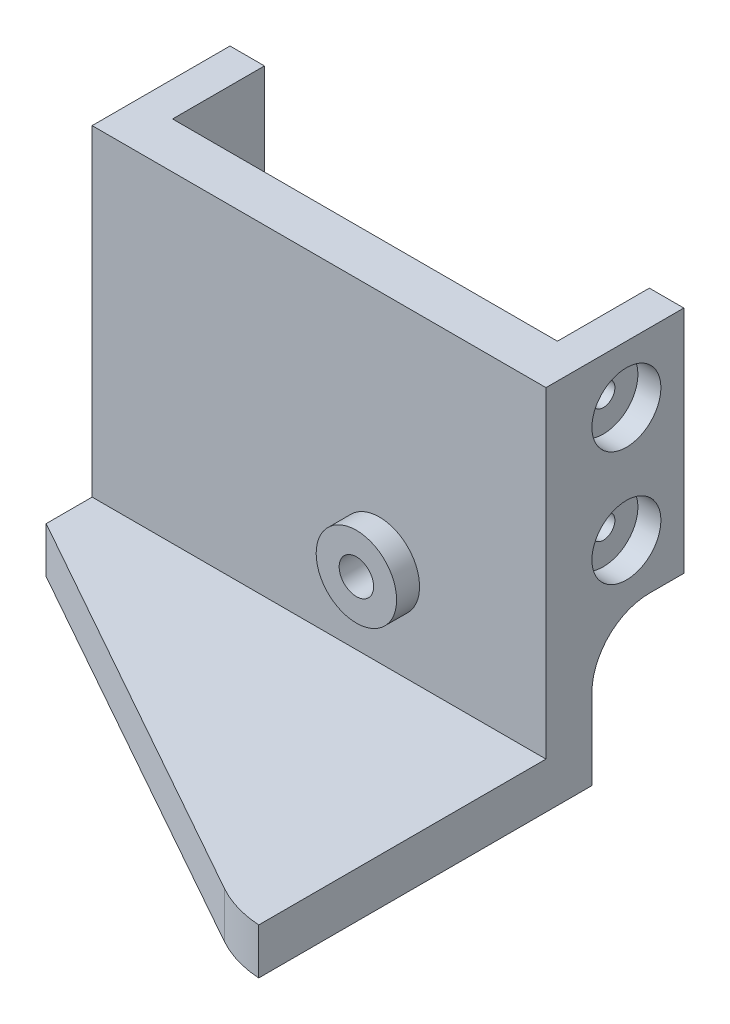
SolidWorks part; units mm, degrees
ref_plane "Front Plane" through (0, 0, 0) normal (0, 0, 1) x (1, 0, 0)
ref_plane "Top Plane" through (0, 0, 0) normal (0, 1, 0) x (1, 0, 0)
ref_plane "Right Plane" through (0, 0, 0) normal (1, 0, 0) x (0, 0, -1)
sketch "Sketch1" plane through (0, 0, 0) normal (0, 1, 0) x (1, 0, 0)
  line L1 (0, 0) -> (37.5, 0)
  line L2 (0, 0) -> (0, 12)
  line L3 (0, 12) -> (37.5, 12)
  line L4 (37.5, 0) -> (37.5, 12)
  line L5 (3, 12) -> (36.5, 12)
  line L6 (3, 12) -> (3, 4)
  line L7 (3, 4) -> (36.5, 4)
  line L8 (36.5, 12) -> (36.5, 4)
  dimension "D1" = 12
  dimension "D2" = 37.5
  dimension "D3" = 33.5
  dimension "D4" = 3
  dimension "D5" = 3
  dimension "10" = 8
extrude "Boss-Extrude1" add sketch "Sketch1" along normal blind 20 contours L3 L8 L7 L6 L2 L1 L4 region at (17.2775, 0, -3.0549)
sketch "Sketch2" plane through (0, 0, 0) normal (0, -1, 0) x (1, 0, 0)
  line L0 (37.5, 0) -> (37.5, -12) construction
  line L1 (0, 0) -> (37.5, 0)
  line L2 (0, 0) -> (0, -4)
  line L3 (0, -4) -> (37.5, -4)
  line L4 (37.5, 0) -> (37.5, -4)
extrude "Boss-Extrude2" add sketch "Sketch2" along normal blind 12
fillet "Fillet1" radius 5 2 edges at (1.5, 0, -4) (37, 0, -4)
sketch "Sketch3" plane through (0, 0, 0) normal (0, 0, 1) x (1, 0, 0)
  line L0 (37.5, 20) -> (37.5, -12) construction
  line L1 (0, -12) -> (37.5, -12)
  line L2 (0, -12) -> (0, -8)
  line L3 (0, -8) -> (37.5, -8)
  line L4 (37.5, -12) -> (37.5, -8)
  dimension "D1" = 4
extrude "Boss-Extrude3" add sketch "Sketch3" along normal blind 25 contours L3 L4 L1 L2
sketch "Sketch4" plane through (0, 0, 0) normal (0, 0, 1) x (1, 0, 0)
  line L0 (0, -8) -> (37.5, -8) construction
  line L1 (0, 20) -> (0, -8) construction
  circle A0 centre (25, -0.5) radius 1.5
  circle A1 centre (25, -0.5) radius 3.5
  dimension "D1" = 3
  dimension "D2" = 7.5
  dimension "D4" = 25
  dimension "D3" = 2
extrude "Boss-Extrude4" add sketch "Sketch4" along normal blind 2
sketch "Sketch5" plane through (0, 0, 2) normal (0, 0, 1) x (1, 0, 0)
  circle A0 centre (25, -0.5) radius 1.5 construction
  circle A1 centre (25, -0.5) radius 1.5
extrude "Cut-Extrude1" cut sketch "Sketch5" against normal through all contours A1
sketch "Sketch6" plane through (0, -8, 0) normal (0, 1, 0) x (1, 0, 0)
  line L0 (37.5, -25) -> (0, -4)
  line L3 (0, -25) -> (0, 0) construction
  line L4 (0, -4) -> (0, -25)
  line L5 (0, -25) -> (37.5, -25)
  dimension "D1" = 4
extrude "Cut-Extrude2" cut sketch "Sketch6" against normal blind 10
sketch "Sketch8" plane through (37.5, 0, 0) normal (1, 0, 0) x (0, 0, -1)
  circle A0 centre (7, 15) radius 1
  circle A1 centre (7, 5) radius 1
  dimension "D2" = 2
  dimension "D1" = 10
extrude "Cut-Extrude3" cut sketch "Sketch8" against normal through all both and the other way through all
sketch "Sketch9" plane through (37.5, 0, 0) normal (1, 0, 0) x (0, 0, -1)
  line L8 (0, 20) -> (0, -8)
  line L9 (0, -8) -> (-25, -8)
  line L10 (-25, -8) -> (-25, -12)
  line L11 (-25, -12) -> (4, -12)
  line L12 (4, -12) -> (4, -5)
  line L13 (9, 0) -> (12, 0)
  line L14 (12, 0) -> (12, 20)
  line L15 (12, 20) -> (0, 20)
  line L16 (0, 20) -> (0, -8)
  line L17 (0, -8) -> (-25, -8)
  line L18 (-25, -8) -> (-25, -12)
  line L19 (-25, -12) -> (4, -12)
  line L20 (4, -12) -> (4, -5)
  line L21 (9, 0) -> (12, 0)
  line L22 (12, 0) -> (12, 20)
  line L23 (12, 20) -> (0, 20)
  circle A0 centre (7, 15) radius 1 construction
  arc A1 (9, 0) -> (4, -5) centre (9, -5) ccw
  arc A2 (9, 0) -> (4, -5) centre (9, -5) ccw
  circle A3 centre (7, 15) radius 1
  circle A4 centre (7, 5) radius 1 construction
  circle A5 centre (7, 5) radius 1
  circle A6 centre (7, 15) radius 3
  circle A7 centre (7, 5) radius 3
  line M14 (0, 20) -> (0, -8)
  line M15 (0, -8) -> (-25, -8)
  line M16 (-25, -8) -> (-25, -12)
  line M17 (-25, -12) -> (4, -12)
  line M18 (4, -12) -> (4, -5)
  arc M19 (4, -5) -> (9, 0) centre (9, -5) cw
  line M20 (9, 0) -> (12, 0)
  line M21 (12, 0) -> (12, 20)
  line M22 (12, 20) -> (0, 20)
  dimension "D1" = 0
  dimension "D2" = 2
extrude "Boss-Extrude5" add sketch "Sketch9" along normal blind 2 contours A7 A6 M22 M14 M15 M16 M17 M18 M19 M20 M21 region at (37.5, 19.5108, -6)
fillet "Fillet2" radius 10 1 edges at (37.5, -10, 25)
